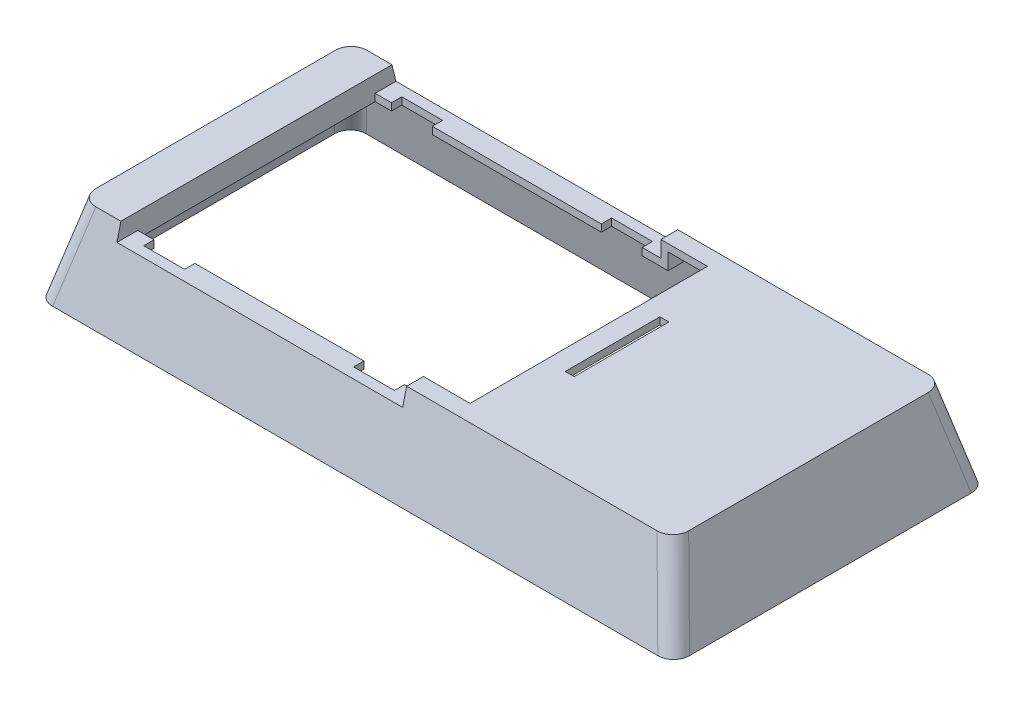
SolidWorks part; units mm, degrees
material "ABS PC"
ref_plane "Front Plane" through (0, 0, 0) normal (0, 0, 1) x (1, 0, 0)
ref_plane "Top Plane" through (0, 0, 0) normal (0, 1, 0) x (1, 0, 0)
ref_plane "Right Plane" through (0, 0, 0) normal (1, 0, 0) x (0, 0, -1)
sketch "Sketch2" plane through (0, 0, 0) normal (0, 1, 0) x (1, 0, 0)
  line L1 (-195, 96) -> (195, 96)
  line L2 (-195, 96) -> (-195, -96)
  line L3 (-195, -96) -> (195, -96)
  line L4 (195, 96) -> (195, -96)
  line L5 (-195, 96) -> (195, -96) construction
  line L6 (-195, -96) -> (195, 96) construction
  point P0 (0, 0)
  dimension "D1" = 192
  dimension "D2" = 390
ref_plane "Plane1" through (0, 53, 0) normal (0, 1, 0) x (1, 0, 0)
sketch "Sketch3" plane through (0, 53, 0) normal (0, 1, 0) x (1, 0, 0)
  line L1 (-181.5, 83) -> (181.5, 83)
  line L2 (-181.5, 83) -> (-181.5, -83)
  line L3 (-181.5, -83) -> (181.5, -83)
  line L4 (181.5, 83) -> (181.5, -83)
  line L5 (-181.5, 83) -> (181.5, -83) construction
  line L6 (-181.5, -83) -> (181.5, 83) construction
  point P0 (0, 0)
  dimension "D1" = 363
  dimension "D2" = 166
loft "Loft1" add profiles "Sketch2", "Sketch3" connector at (195, 0, -96) connector at (181.5, 53, -83)
sketch "Sketch4" plane through (0, 0, 0) normal (0, 0, 1) x (1, 0, 0)
  line L0 (-156.5, 53) -> (-156.5, 43)
  line L1 (-181.5, 53) -> (181.5, 53) construction
  line L2 (-156.5, 43) -> (18.5, 43)
  line L3 (18.5, 43) -> (18.5, 53)
  line L4 (18.5, 53) -> (-156.5, 53)
  dimension "D1" = 25
  dimension "D2" = 175
  dimension "D3" = 10
extrude "Cut-Extrude1" cut sketch "Sketch4" against normal up to surface and the other way up to surface up to face at (94.125, 13.25, -92.75) other way up to face at (-94.125, 13.25, 92.75)
shell "Shell1" thickness 4.4 removed face at (0, 0, 0)
sketch "Sketch5" plane through (0, 53, 0) normal (0, 1, 0) x (1, 0, 0)
  line L21 (47, -72.7) -> (47, 72.7)
  line L22 (47, 72.7) -> (7, 72.7)
  line L23 (7, 72.7) -> (7, 79)
  line L24 (7, 79) -> (-18, 79)
  line L25 (-18, 79) -> (-18, 72.7)
  line L26 (-18, 72.7) -> (-121.5, 72.7)
  line L27 (-121.5, 72.7) -> (-121.5, 79)
  line L28 (-121.5, 79) -> (-146.5, 79)
  line L29 (-146.5, 79) -> (-146.5, 72.7)
  line L30 (-146.5, 72.7) -> (-156.5, 72.7)
  line L31 (-156.5, 72.7) -> (-156.5, -72.7)
  line L32 (-156.5, -72.7) -> (-146.5, -72.7)
  line L33 (-146.5, -72.7) -> (-146.5, -79)
  line L34 (-146.5, -79) -> (-121.5, -79)
  line L35 (-121.5, -79) -> (-121.5, -72.7)
  line L36 (-121.5, -72.7) -> (-18, -72.7)
  line L37 (-18, -72.7) -> (-18, -79)
  line L38 (-18, -79) -> (7, -79)
  line L39 (7, -79) -> (7, -72.7)
  line L40 (7, -72.7) -> (47, -72.7)
  line L41 (47, -72.7) -> (47, 72.7)
  line L42 (47, 72.7) -> (7, 72.7)
  line L43 (7, 72.7) -> (7, 79)
  line L44 (7, 79) -> (-18, 79)
  line L45 (-18, 79) -> (-18, 72.7)
  line L46 (-18, 72.7) -> (-121.5, 72.7)
  line L47 (-121.5, 72.7) -> (-121.5, 79)
  line L48 (-121.5, 79) -> (-146.5, 79)
  line L49 (-146.5, 79) -> (-146.5, 72.7)
  line L50 (-146.5, 72.7) -> (-156.5, 72.7)
  line L51 (-156.5, 72.7) -> (-156.5, -72.7)
  line L52 (-156.5, -72.7) -> (-146.5, -72.7)
  line L53 (-146.5, -72.7) -> (-146.5, -79)
  line L54 (-146.5, -79) -> (-121.5, -79)
  line L55 (-121.5, -79) -> (-121.5, -72.7)
  line L56 (-121.5, -72.7) -> (-18, -72.7)
  line L57 (-18, -72.7) -> (-18, -79)
  line L58 (-18, -79) -> (7, -79)
  line L59 (7, -79) -> (7, -72.7)
  line L60 (7, -72.7) -> (47, -72.7)
  dimension "D1" = 0
extrude "Cut-Extrude2" cut sketch "Sketch5" against normal through all
fillet "Fillet1" radius 10 8 edges at (-184.2699, 24.3, -85.5092) (-184.2699, 24.3, 85.5092) (184.2699, 24.3, 85.5092) (184.2699, 24.3, -85.5092)
sketch "Sketch6" plane through (0, 53, 0) normal (0, 1, 0) x (1, 0, 0)
  line L2 (56.6692, -81.5291) -> (65.8169, -81.5291)
  line L3 (65.8169, -81.5291) -> (65.8169, -25)
  line L4 (65.8169, -25) -> (56.6692, -25)
  line L5 (56.6692, -25) -> (56.6692, -81.5291)
  line L6 (57.6692, -80.5291) -> (64.8169, -80.5291)
  line L7 (64.8169, -80.5291) -> (64.8169, -26)
  line L8 (64.8169, -26) -> (57.6692, -26)
  line L9 (57.6692, -26) -> (57.6692, -80.5291)
  line L11 (64.8169, -80.5291) -> (64.8169, -26) construction
  line L13 (57.6692, -26) -> (57.6692, -80.5291) construction
  line L24 (57.6692, -80.5291) -> (64.8169, -80.5291)
  line L28 (64.8169, -26) -> (57.6692, -26) construction
  line L29 (64.8169, -26) -> (57.6692, -26)
  line L30 (57.6692, -80.5291) -> (64.8169, -80.5291) construction
  dimension "D1" = 0
  dimension "D2" = 1
extrude "Cut-Extrude3" [suppressed] cut sketch "Sketch6" against normal blind 5 and the other way blind 1
sketch "Sketch7" plane through (0, 53, 0) normal (0, 1, 0) x (1, 0, 0)
  line L1 (47, -72.7) -> (47, 72.7) construction
  line L4 (59.2, 31.3699) -> (64.7, 31.3699)
  line L5 (59.2, 31.3699) -> (59.2, -26.6301)
  line L6 (59.2, -26.6301) -> (64.7, -26.6301)
  line L7 (64.7, 31.3699) -> (64.7, -26.6301)
  point P6 (61.95, 2.3699)
  dimension "D1" = 12.2
  dimension "D2" = 5.5
  dimension "D3" = 58
extrude "Cut-Extrude4" cut sketch "Sketch7" against normal blind 10
sketch3d "3DSketch1"
  line L0 (-156.5, 43, -72.7) -> (-146.5, 43, -72.7) construction
  line L1 (-156.5, 43, -72.7) -> (-146.5, 43, -72.7)
  line L2 (-146.5, 43, -79) -> (-121.5, 43, -79) construction
  line L4 (-146.5, 43, -79) -> (-121.5, 43, -79)
  line L5 (-146.5, 43, -72.7) -> (-146.5, 43, -79) construction
  line L6 (-146.5, 43, -72.7) -> (-146.5, 43, -79)
  line L7 (-121.5, 43, -79) -> (-121.5, 43, -72.7) construction
  line L8 (-121.5, 43, -79) -> (-121.5, 43, -72.7)
  line L9 (-121.5, 43, -72.7) -> (-18, 43, -72.7) construction
  line L10 (-121.5, 43, -72.7) -> (-18, 43, -72.7)
  line L11 (18.5, 43, -72.7) -> (18.5, 53, -72.7) construction
  line L12 (7, 43, -72.7) -> (18.5, 43, -72.7) construction
  line L13 (7, 43, -79) -> (7, 43, -72.7) construction
  line L14 (-18, 43, -79) -> (7, 43, -79) construction
  line L15 (-18, 43, -72.7) -> (-18, 43, -79) construction
  line L16 (18.5, 43, -72.7) -> (18.5, 53, -72.7)
  line L17 (7, 43, -72.7) -> (18.5, 43, -72.7)
  line L18 (7, 43, -79) -> (7, 43, -72.7)
  line L19 (-18, 43, -79) -> (7, 43, -79)
  line L20 (-18, 43, -72.7) -> (-18, 43, -79)
  line L21 (47, 53, 72.7) -> (47, 53, -72.7) construction
  line L22 (47, 53, -72.7) -> (18.5, 53, -72.7) construction
  line L23 (47, 53, 72.7) -> (47, 53, -72.7)
  line L24 (47, 53, -72.7) -> (18.5, 53, -72.7)
  line L25 (-18, 43, 72.7) -> (-121.5, 43, 72.7) construction
  line L26 (-18, 43, 79) -> (-18, 43, 72.7) construction
  line L27 (7, 43, 79) -> (-18, 43, 79) construction
  line L28 (7, 43, 72.7) -> (7, 43, 79) construction
  line L29 (18.5, 43, 72.7) -> (7, 43, 72.7) construction
  line L30 (18.5, 53, 72.7) -> (18.5, 43, 72.7) construction
  line L31 (18.5, 53, 72.7) -> (47, 53, 72.7) construction
  line L32 (-18, 43, 72.7) -> (-121.5, 43, 72.7)
  line L33 (-18, 43, 79) -> (-18, 43, 72.7)
  line L34 (7, 43, 79) -> (-18, 43, 79)
  line L35 (7, 43, 72.7) -> (7, 43, 79)
  line L36 (18.5, 43, 72.7) -> (7, 43, 72.7)
  line L37 (18.5, 53, 72.7) -> (18.5, 43, 72.7)
  line L38 (18.5, 53, 72.7) -> (47, 53, 72.7)
  line L39 (-146.5, 43, 72.7) -> (-156.5, 43, 72.7) construction
  line L40 (-146.5, 43, 79) -> (-146.5, 43, 72.7) construction
  line L41 (-121.5, 43, 79) -> (-146.5, 43, 79) construction
  line L42 (-121.5, 43, 72.7) -> (-121.5, 43, 79) construction
  line L43 (-146.5, 43, 72.7) -> (-156.5, 43, 72.7)
  line L44 (-146.5, 43, 79) -> (-146.5, 43, 72.7)
  line L45 (-121.5, 43, 79) -> (-146.5, 43, 79)
  line L46 (-121.5, 43, 72.7) -> (-121.5, 43, 79)
  line L50 (-156.5, 43, -72.7) -> (-156.5, 43, 72.7)
sweep "Sweep1" [suppressed] add path "3DSketch1" circular profile diameter 1 parameters "D3"=1
sketch "Sketch32" plane through (0, 53, 0) normal (0, 1, 0) x (1, 0, 0)
  line L0 (59.2, -26.6301) -> (64.7, -26.6301) construction
  line L1 (59.2, 31.3699) -> (59.2, -26.6301) construction
  line L2 (64.7, -26.6301) -> (64.7, 31.3699) construction
  line L3 (64.7, 31.3699) -> (59.2, 31.3699) construction
  line L4 (59.2, -26.6301) -> (64.7, -26.6301)
  line L5 (59.2, 31.3699) -> (59.2, -26.6301)
  line L6 (64.7, -26.6301) -> (64.7, 31.3699)
  line L7 (64.7, 31.3699) -> (59.2, 31.3699)
